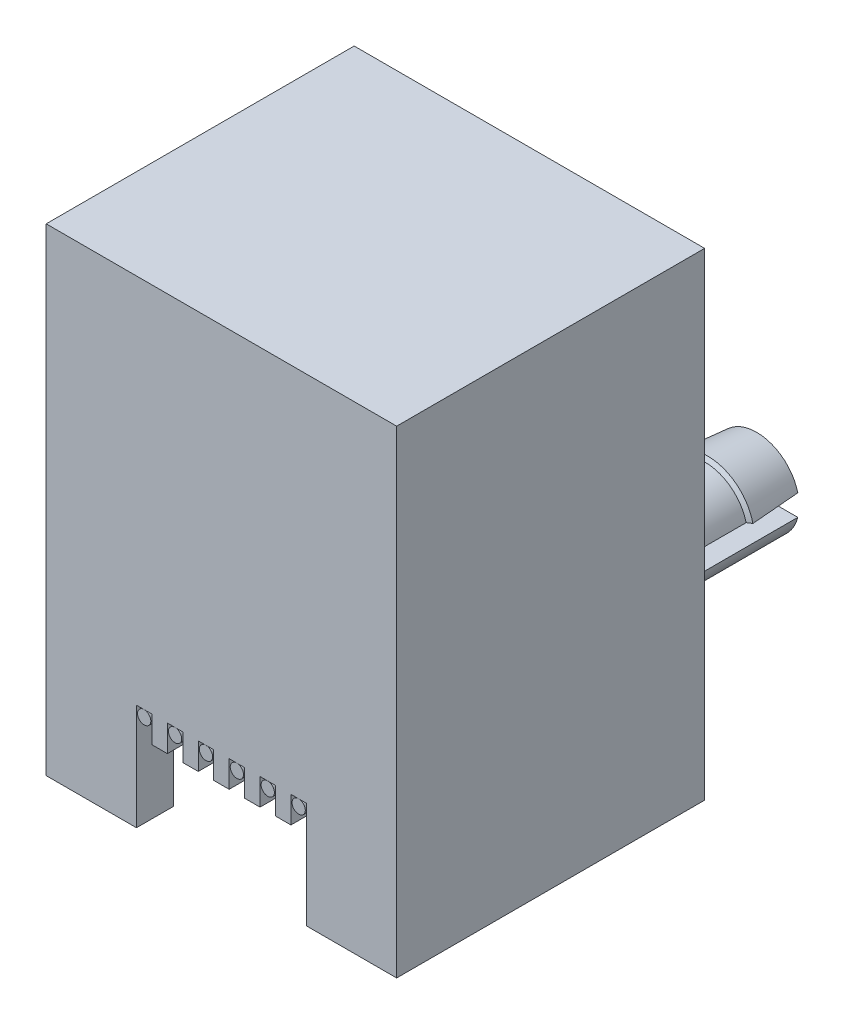
SolidWorks part; units mm, degrees
material "ABS PC"
ref_plane "Front Plane" through (0, 0, 0) normal (0, 0, 1) x (1, 0, 0)
ref_plane "Top Plane" through (0, 0, 0) normal (0, 1, 0) x (1, 0, 0)
ref_plane "Right Plane" through (0, 0, 0) normal (1, 0, 0) x (0, 0, -1)
sketch "Sketch1" plane through (0, 0, 0) normal (0, 1, 0) x (1, 0, 0)
  line L0 (6.6, -5.8) -> (6.6, 5.8)
  line L1 (-6.6, -5.8) -> (6.6, -5.8)
  line L2 (-6.6, -5.8) -> (-6.6, 5.8)
  line L3 (6.6, 5.8) -> (-6.6, 5.8)
  line L4 (-6.6, 0) -> (6.6, 0) construction
  line L5 (0, 5.8) -> (0, -5.8) construction
  dimension "D1" = 13.2
  dimension "D2" = 11.6
extrude "Extrude1" add sketch "Sketch1" along normal mid plane 18
sketch "Sketch2" plane through (0, -9, 0) normal (0, -1, 0) x (1, 0, 0)
  line L0 (-6.6, 5.8) -> (6.6, 5.8) construction
  line L1 (5.2, 4.4) -> (-5.2, 4.4)
  line L2 (5.2, -2.8) -> (5.2, 4.4)
  line L3 (5.2, -2.8) -> (3.8, -2.8)
  line L4 (3.8, -4.6) -> (3.8, -2.8)
  line L5 (3.8, -4.6) -> (-3.8, -4.6)
  line L6 (6.6, -5.8) -> (-6.6, -5.8) construction
  line L7 (0, -5.8) -> (0, 5.8) construction
  line L11 (-3.8, -4.6) -> (-3.8, -2.8)
  line L12 (-5.2, -2.8) -> (-3.8, -2.8)
  line L13 (-5.2, -2.8) -> (-5.2, 4.4)
  dimension "D1" = 1.4
  dimension "D2" = 7.6
  dimension "D4" = 7.2
  dimension "D5" = 1.4
  dimension "D6" = 1.8
extrude "Cut-Extrude1" cut sketch "Sketch2" against normal blind 10
sketch "Sketch3" plane through (0, 0, 5.8) normal (0, 0, 1) x (1, 0, 0)
  line L0 (-3.2, -9) -> (-3.2, -6)
  line L1 (-3.2, -6) -> (3.2, -6)
  line L2 (3.2, -6) -> (3.2, -9)
  line L3 (3.2, -9) -> (-3.2, -9)
  line L4 (0, -9) -> (0, -6) construction
  line L5 (-6.6, -9) -> (6.6, -9) construction
  dimension "D1" = 6.4
  dimension "D2" = 3
extrude "Cut-Extrude2" cut sketch "Sketch3" against normal up to surface (1.4 mm away) up to face at (0, -4, 4.4)
sketch "Sketch4" plane through (0, 0, -5.8) normal (0, 0, -1) x (-1, 0, 0)
  line L0 (2.4, -7.2) -> (2.4, -9)
  line L1 (3.2, -7.2) -> (2.4, -7.2)
  line L2 (3.2, -4.2) -> (3.2, -7.2)
  line L3 (-3.2, -4.2) -> (3.2, -4.2)
  line L4 (-3.2, -7.2) -> (-3.2, -4.2)
  line L5 (-2.4, -7.2) -> (-3.2, -7.2)
  line L6 (-2.4, -9) -> (-2.4, -7.2)
  line L7 (2.4, -9) -> (-2.4, -9)
  line L8 (0, -9) -> (0, -4.2) construction
  line L9 (-6.6, -9) -> (6.6, -9) construction
  dimension "D1" = 6.4
  dimension "D2" = 4.8
  dimension "D3" = 1.8
  dimension "D4" = 3
extrude "Cut-Extrude3" cut sketch "Sketch4" against normal up to surface (1.2 mm away) up to face at (0, -4, -4.6)
sketch "Sketch5" plane through (0, 0, -5.8) normal (0, 0, -1) x (-1, 0, 0)
  line L4 (-6.6, -9) -> (-2.4, -9) construction
  line L5 (-6.6, 9) -> (-6.6, -9) construction
  line L6 (-5.66, -1.12) -> (-3.46, -1.12) construction
  line L7 (-6.6092, -1.52) -> (-3.5108, -1.52)
  line L8 (-6.6092, -0.72) -> (-3.5108, -0.72)
  line L9 (-5.66, -0.72) -> (-3.46, -0.72) construction
  line L10 (-5.66, -1.52) -> (-3.46, -1.52) construction
  arc A1 (-6.6092, -1.52) -> (-3.5108, -1.52) centre (-5.06, -1.12) ccw
  arc A2 (-3.5108, -0.72) -> (-6.6092, -0.72) centre (-5.06, -1.12) ccw
  dimension "D2" = 3.2
  dimension "D3" = 7.88
  dimension "D5" = 1.54
  dimension "D6" = 0.4
  dimension "D7" = 0.4
extrude "Extrude2" add sketch "Sketch5" along normal blind 3.5
ref_plane "Plane1" through (0, 0, -7.4537) normal (0, 0, -1) x (-1, 0, 0)
sketch "Sketch6" plane through (0, 0, -7.4537) normal (0, 0, -1) x (-1, 0, 0)
  line L1 (-6.6092, -0.72) -> (-3.5108, -0.72) construction
  line L2 (-6.7637, -0.72) -> (-3.3563, -0.72)
  arc A0 (-3.3563, -0.72) -> (-6.7637, -0.72) centre (-5.06, -1.12) ccw
  arc A1 (-3.5108, -0.72) -> (-6.6092, -0.72) centre (-5.06, -1.12) ccw construction
  dimension "D1" = 3.5
ref_plane "Plane2" through (0, 0, -7.3537) normal (0, 0, -1) x (-1, 0, 0)
sketch "Sketch7" plane through (0, 0, -7.3537) normal (0, 0, -1) x (-1, 0, 0)
  line L0 (-6.6092, -0.72) -> (-3.5108, -0.72) construction
  line L1 (-6.6092, -0.72) -> (-3.5108, -0.72)
  arc A0 (-3.5108, -0.72) -> (-6.6092, -0.72) centre (-5.06, -1.12) ccw construction
  arc A1 (-3.5108, -0.72) -> (-6.6092, -0.72) centre (-5.06, -1.12) ccw
sketch "Sketch8" plane through (0, 0, -9.3) normal (0, 0, -1) x (-1, 0, 0)
  line L0 (-6.6092, -0.72) -> (-3.5108, -0.72) construction
  line L1 (-6.6092, -0.72) -> (-3.5108, -0.72)
  arc A0 (-3.5108, -0.72) -> (-6.6092, -0.72) centre (-5.06, -1.12) ccw construction
  arc A1 (-3.5108, -0.72) -> (-6.6092, -0.72) centre (-5.06, -1.12) ccw
loft "Loft1" add profiles "Sketch8", "Sketch6" start constraint default connector at (6.6092, -0.72, -9.3) connector at (6.7637, -0.72, -7.4537)
loft "Loft2" add profiles "Sketch6<2>", "Sketch7" connector at (3.3563, -0.72, -7.4537) connector at (3.5108, -0.72, -7.3537)
sketch "Sketch6<2>" plane through (0, 0, -7.4537) normal (0, 0, -1) x (-1, 0, 0) same geometry as "Sketch6"
mirror "Mirror1" about plane through (0, 0, 0) normal (1, 0, 0) of "Extrude2", "Loft1", "Loft2"
sketch "Sketch9" plane through (0, 0, 4.4) normal (0, 0, -1) x (-1, 0, 0)
  line L0 (3.2, -6) -> (-3.2, -6) construction
  line L1 (3.2, -6) -> (2.6182, -6)
  line L2 (3.2, -6) -> (3.2, -5)
  line L3 (3.2, -5) -> (2.6182, -5)
  line L4 (2.6182, -6) -> (2.6182, -5)
  line L5 (2.0364, -6) -> (1.4545, -6)
  line L6 (2.0364, -6) -> (2.0364, -5)
  line L7 (2.0364, -5) -> (1.4545, -5)
  line L8 (1.4545, -6) -> (1.4545, -5)
  line L9 (3.2, -5.5) -> (2.6182, -5.5) construction
  line L10 (0.8727, -6) -> (0.2909, -6)
  line L11 (0.8727, -6) -> (0.8727, -5)
  line L12 (0.8727, -5) -> (0.2909, -5)
  line L13 (0.2909, -6) -> (0.2909, -5)
  line L14 (-0.2909, -6) -> (-0.8727, -6)
  line L15 (-0.2909, -6) -> (-0.2909, -5)
  line L16 (-0.2909, -5) -> (-0.8727, -5)
  line L17 (-0.8727, -6) -> (-0.8727, -5)
  line L18 (-1.4545, -6) -> (-2.0364, -6)
  line L19 (-1.4545, -6) -> (-1.4545, -5)
  line L20 (-1.4545, -5) -> (-2.0364, -5)
  line L21 (-2.0364, -6) -> (-2.0364, -5)
  line L22 (-2.6182, -6) -> (-3.2, -6)
  line L23 (-2.6182, -6) -> (-2.6182, -5)
  line L24 (-2.6182, -5) -> (-3.2, -5)
  line L25 (-3.2, -6) -> (-3.2, -5)
  line L26 (2.6182, -5.5) -> (2.0364, -5.5) construction
  line L27 (2.0364, -5.5) -> (1.4545, -5.5) construction
  line L28 (1.4545, -5.5) -> (0.8727, -5.5) construction
  line L29 (0.8727, -5.5) -> (0.2909, -5.5) construction
  line L30 (0.2909, -5.5) -> (-0.2909, -5.5) construction
  line L31 (-0.2909, -5.5) -> (-0.8727, -5.5) construction
  line L32 (-0.8727, -5.5) -> (-1.4545, -5.5) construction
  line L33 (-1.4545, -5.5) -> (-2.0364, -5.5) construction
  line L34 (-2.0364, -5.5) -> (-2.6182, -5.5) construction
  line L35 (-2.6182, -5.5) -> (-3.2, -5.5) construction
  dimension "D1" = 1
extrude "Cut-Extrude4" cut sketch "Sketch9" against normal up to surface (1.4 mm away) up to face at (0, -3.75, 5.8)
sketch "Sketch10" plane through (0, 1, 0) normal (0, -1, 0) x (1, 0, 0)
  line L2 (-3.3, -2.8) -> (-3.3, -4.6)
  line L3 (-3.3, -2.8) -> (-3.3, -4.6) construction
  line L5 (-3.8, -4.1) -> (3.8, -4.1)
  line L6 (-3.8, -4.1) -> (3.8, -4.1) construction
  line L7 (-3.3, -4.1) -> (-3.3, 0)
  line L8 (3.3, -4.6) -> (3.3, -2.8)
  line L9 (3.3, -4.6) -> (3.3, -2.8) construction
  line L10 (-3.3, 0) -> (3.3, 0)
  line L11 (3.3, 0) -> (3.3, -4.1)
  line L12 (3.3, -4.1) -> (-3.3, -4.1)
  dimension "D1" = 0.5
  dimension "D2" = 0.5
  dimension "D3" = 0.5
extrude "Cut-Extrude5" cut sketch "Sketch10" against normal blind 0.3
sketch "Sketch11" plane through (0, 1, 0) normal (0, -1, 0) x (1, 0, 0)
  line L0 (2.6182, 4.4) -> (3.2, 4.4) construction
  line L1 (1.4545, 4.4) -> (2.0364, 4.4) construction
  line L2 (0.2909, 4.4) -> (0.8727, 4.4) construction
  line L3 (-0.8727, 4.4) -> (-0.2909, 4.4) construction
  line L4 (-2.0364, 4.4) -> (-1.4545, 4.4) construction
  line L5 (-3.2, 4.4) -> (-2.6182, 4.4) construction
  line L6 (2.6182, 4.4) -> (3.2, 4.4)
  line L7 (1.4545, 4.4) -> (2.0364, 4.4)
  line L8 (0.2909, 4.4) -> (0.8727, 4.4)
  line L9 (-0.8727, 4.4) -> (-0.2909, 4.4)
  line L10 (-2.0364, 4.4) -> (-1.4545, 4.4)
  line L11 (-3.2, 4.4) -> (-2.6182, 4.4)
  line L12 (-3.3, -2.05) -> (3.2, -2.05) construction
  line L13 (-3.3, 0) -> (-3.3, -4.1) construction
  line L15 (-3.2, 4.4) -> (-3.2, -2.05)
  line L16 (-3.2, -2.05) -> (-2.6182, -2.05)
  line L17 (-2.6182, -2.05) -> (-2.6182, 4.4)
  line L18 (-2.0364, 4.4) -> (-2.0364, -2.05)
  line L19 (-2.0364, -2.05) -> (-1.4545, -2.05)
  line L20 (-1.4545, -2.05) -> (-1.4545, 4.4)
  line L21 (-0.8727, 4.4) -> (-0.8727, -2.05)
  line L22 (-0.8727, -2.05) -> (-0.2909, -2.05)
  line L23 (-0.2909, -2.05) -> (-0.2909, 4.4)
  line L24 (0.2909, 4.4) -> (0.2909, -2.05)
  line L25 (0.2909, -2.05) -> (0.8727, -2.05)
  line L26 (0.8727, -2.05) -> (0.8727, 4.4)
  line L27 (1.4545, 4.4) -> (1.4545, -2.05)
  line L28 (1.4545, -2.05) -> (2.0364, -2.05)
  line L29 (2.0364, -2.05) -> (2.0364, 4.4)
  line L30 (2.6182, 4.4) -> (2.6182, -2.05)
  line L31 (3.2, 4.4) -> (3.2, -2.05)
  line L32 (3.2, -2.05) -> (2.6182, -2.05)
extrude "Cut-Extrude6" cut sketch "Sketch11" against normal blind 0.6
ref_plane "Plane3" through (-2.9091, 0, 0) normal (1, 0, 0) x (0, 0, -1)
sketch "Sketch13" plane through (-2.9091, 0, 0) normal (1, 0, 0) x (0, 0, -1)
  line L0 (-5.8, -5) -> (-4.8195, -5)
  line L1 (-4.3271, -4.5868) -> (-3.2362, 1.6)
  line L2 (-5.8, -5) -> (-4.4, -5) construction
  line L3 (-5.8, -5) -> (-5.8, -9) construction
  line L4 (-4.4, 1.6) -> (2.05, 1.6) construction
  arc A0 (-4.8195, -5) -> (-4.3271, -4.5868) centre (-4.8195, -4.5) ccw
  point P12 (-4.4, -5)
  dimension "D2" = 0.5
  dimension "D1" = 100
sketch "Sketch14" plane through (0, 0, 5.8) normal (0, 0, 1) x (1, 0, 0)
  circle A0 centre (-2.9091, -5.25) radius 0.25
  point P0 (-2.9091, -5)
  dimension "D1" = 0.5
sweep "Sweep1" add profiles "Sketch14" path "Sketch13"
pattern_linear "LPattern1" count 6 spacing 1.1636 along (1, 0, 0) of bodies 112
ref_plane "Plane4" through (0, 0, 1) normal (0, 0, -1) x (-1, 0, 0)
sketch "Sketch15" plane through (0, 0, 1) normal (0, 0, -1) x (-1, 0, 0)
  line L0 (0, -20) -> (0, 0) construction
  dimension "D1" = 20
ref_axis "Axis1" through (0, 0, 1) along (0, -1, 0)
